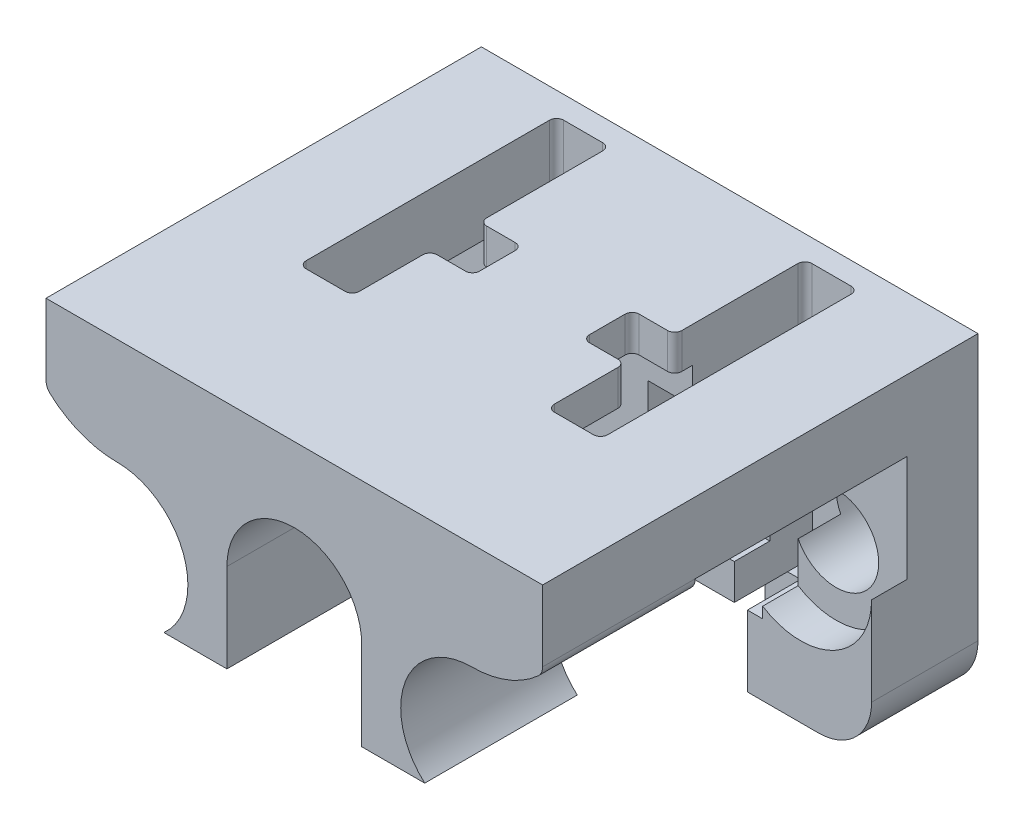
SolidWorks part; units mm, degrees
ref_plane "Front Plane" through (0, 0, 0) normal (0, 0, 1) x (1, 0, 0)
ref_plane "Top Plane" through (0, 0, 0) normal (0, 1, 0) x (1, 0, 0)
ref_plane "Right Plane" through (0, 0, 0) normal (1, 0, 0) x (0, 0, -1)
sketch "Sketch1" plane through (0, 0, 0) normal (0, 0, 1) x (1, 0, 0)
  line L1 (-7, -3.5) -> (7, -3.5)
  line L2 (-7, -3.5) -> (-7, 3.5)
  line L3 (-7, 3.5) -> (7, 3.5)
  line L4 (7, -3.5) -> (7, 3.5)
  line L5 (-7, -3.5) -> (7, 3.5) construction
  line L6 (-7, 3.5) -> (7, -3.5) construction
  point P0 (0, 0)
  dimension "D1" = 14
  dimension "D2" = 7
extrude "Boss-Extrude1" add sketch "Sketch1" along normal blind 2
fillet "Fillet1" radius 1.5 2 edges at (-7, -3.5, 1) (7, -3.5, 1)
hole_wizard "M2 Clearance Hole1" positions "Sketch2" profile "Sketch3" hole size "M2" standard "ISO" end condition through all
sketch "Sketch2" plane through (0, 0, 2) normal (0, 0, 1) x (1, 0, 0)
  line L0 (7, 3.5) -> (-7, 3.5) construction
  line L1 (0, 0) -> (0, 2.7622) construction
  point P0 (-5, 0.5)
  point P2 (5, 0.5)
  dimension "D1" = 3
  dimension "D2" = 10
sketch "Sketch3" plane through (-5, 0.5, 2) normal (1, 0, 0) x (0, -1, 0)
  line L0 (0, 0) -> (0, 2)
  line L1 (0, 2) -> (1.2, 2)
  line L2 (1.2, 2) -> (1.2, 0)
  line L5 (1.2, 0) -> (0, 0)
  line L11 (0, -6.35) -> (0, 107.95) construction
  dimension "Thru Hole Dia." = 2.4
  dimension "Thru Hole Depth" = 2
sketch "Sketch4" plane through (0, 3.5, 0) normal (0, 1, 0) x (1, 0, 0)
  line L0 (7, 0) -> (-7, 0) construction
  line L1 (-7, 0) -> (7, 0)
  line L2 (-7, 0) -> (-7, -12.2738)
  line L3 (-7, -12.2738) -> (7, -12.2738)
  line L4 (7, 0) -> (7, -12.2738)
extrude "Boss-Extrude2" add sketch "Sketch4" along normal blind 2
sketch "Sketch5" plane through (0, 0, 2) normal (0, 0, 1) x (1, 0, 0)
  line L0 (-5.5, -3.5) -> (5.5, -3.5) construction
  line L1 (-5.5, -3.5) -> (5.5, -3.5)
  line L2 (7, -2) -> (7, 3.5) construction
  line L3 (-7, 3.5) -> (-7, -2) construction
  line L4 (7, -2) -> (7, 3.5)
  line L5 (-7, 3.5) -> (-7, -2)
  line L6 (-3.2679, -0.5) -> (3.2679, -0.5)
  arc A0 (5.5, -3.5) -> (7, -2) centre (5.5, -2) ccw construction
  arc A1 (-7, -2) -> (-5.5, -3.5) centre (-5.5, -2) ccw construction
  arc A2 (5.5, -3.5) -> (7, -2) centre (5.5, -2) ccw
  arc A3 (-7, -2) -> (-5.5, -3.5) centre (-5.5, -2) ccw
  circle A4 centre (-5, 0.5) radius 2
  circle A5 centre (5, 0.5) radius 2
  arc M7 (-7, -2) -> (-5.5, -3.5) centre (-5.5, -2) ccw
  line M8 (-5.5, -3.5) -> (5.5, -3.5)
  arc M9 (5.5, -3.5) -> (7, -2) centre (5.5, -2) ccw
  line M10 (7, -2) -> (7, 3.5)
  dimension "D1" = 3
extrude "Boss-Extrude3" add sketch "Sketch5" along normal blind 1 contours A5 L6 A4 L5 M7 M8 M9 M10 region at (0, -2.1082, 2)
sketch "Sketch6" plane through (0, 0, 0) normal (0, 0, -1) x (-1, 0, 0)
  line L0 (5.5, -3.5) -> (-5.5, -3.5) construction
  line L1 (-2.5, -3.5) -> (2.5, -3.5)
  line L2 (-2.5, -3.5) -> (-2.5, 0)
  line L3 (-2.5, 0) -> (2.5, 0)
  line L4 (2.5, -3.5) -> (2.5, 0)
  line L5 (5.5, -3.5) -> (-5.5, -3.5) construction
  point P11 (0, -3.5)
  dimension "D1" = 5
  dimension "D2" = 3.5
extrude "Cut-Extrude1" cut sketch "Sketch6" against normal blind 1.5
sketch "Sketch7" plane through (0, 0, 1.5) normal (0, 0, -1) x (-1, 0, 0)
  line L1 (-3.5, -3.5) -> (3.5, -3.5)
  line L2 (-3.5, -3.5) -> (-3.5, -1.5)
  line L3 (-3.5, -1.5) -> (3.5, -1.5)
  line L4 (3.5, -3.5) -> (3.5, -1.5)
  line L5 (-2.5, -3.5) -> (-5.5, -3.5) construction
  point P5 (0, -3.5)
  dimension "D1" = 2
  dimension "D2" = 7
extrude "Cut-Extrude2" cut sketch "Sketch7" against normal up to next
sketch "Sketch8" plane through (0, 0, 2) normal (0, 0, 1) x (1, 0, 0)
  line L1 (-1.5, -1.5) -> (1.5, -1.5)
  line L2 (-1.5, -1.5) -> (-1.5, 3.5)
  line L3 (-1.5, 3.5) -> (1.5, 3.5)
  line L4 (1.5, -1.5) -> (1.5, 3.5)
  line L5 (7, 3.5) -> (-7, 3.5) construction
  line L6 (-3.5, -1.5) -> (3.5, -1.5) construction
  circle A0 centre (-5, 0.5) radius 2
  circle A1 centre (5, 0.5) radius 2
  arc A2 (3.2679, -0.5) -> (7, 0.5) centre (5, 0.5) ccw construction
  point P17 (0, -1.5)
  line M8 (-3.2679, -0.5) -> (3.2679, -0.5)
  line M12 (7, 3.5) -> (-7, 3.5)
  dimension "D1" = 3
extrude "Boss-Extrude4" add sketch "Sketch8" along normal blind 1.8 contours L4 L2 M8 M12 | L1 L4 L2 M8 region at (0, -1, 2) region at (0, 1.5, 2)
sketch "Sketch9" plane through (0, 5.5, 0) normal (0, 1, 0) x (1, 0, 0)
  line L0 (7, 0) -> (-7, 0) construction
  line L1 (-2.95, -7.89) -> (-4.05, -7.89)
  line L2 (-2.75, -7.69) -> (-2.75, -5.9)
  line L3 (-2.95, -0.63) -> (-4.05, -0.63)
  line L4 (-4.25, -7.69) -> (-4.25, -0.83)
  line L5 (-7, 0) -> (-7, -12.2738) construction
  line L6 (0, 0) -> (0, -11.1853) construction
  line L11 (-2.55, -5.7) -> (-1.75, -5.7)
  line L12 (-1.55, -5.5) -> (-1.55, -4.5)
  line L13 (-1.75, -4.3) -> (-2.55, -4.3)
  line L14 (-2.75, -4.1) -> (-2.75, -0.83)
  line L15 (2.75, -4.1) -> (2.75, -0.83)
  line L16 (1.75, -4.3) -> (2.55, -4.3)
  line L17 (1.55, -5.5) -> (1.55, -4.5)
  line L18 (2.55, -5.7) -> (1.75, -5.7)
  line L19 (4.25, -7.69) -> (4.25, -0.83)
  line L20 (2.95, -0.63) -> (4.05, -0.63)
  line L21 (2.75, -7.69) -> (2.75, -5.9)
  line L22 (2.95, -7.89) -> (4.05, -7.89)
  arc A0 (-2.95, -7.89) -> (-2.75, -7.69) centre (-2.95, -7.69) ccw
  arc A1 (-2.75, -0.83) -> (-2.95, -0.63) centre (-2.95, -0.83) ccw
  arc A2 (-4.05, -0.63) -> (-4.25, -0.83) centre (-4.05, -0.83) ccw
  arc A3 (-4.05, -7.89) -> (-4.25, -7.69) centre (-4.05, -7.69) cw
  arc A8 (-2.55, -5.7) -> (-2.75, -5.9) centre (-2.55, -5.9) ccw
  arc A9 (-1.75, -5.7) -> (-1.55, -5.5) centre (-1.75, -5.5) ccw
  arc A10 (-1.55, -4.5) -> (-1.75, -4.3) centre (-1.75, -4.5) ccw
  arc A11 (-2.55, -4.3) -> (-2.75, -4.1) centre (-2.55, -4.1) cw
  arc A12 (2.55, -4.3) -> (2.75, -4.1) centre (2.55, -4.1) ccw
  arc A13 (1.55, -4.5) -> (1.75, -4.3) centre (1.75, -4.5) cw
  arc A14 (1.75, -5.7) -> (1.55, -5.5) centre (1.75, -5.5) cw
  arc A15 (2.55, -5.7) -> (2.75, -5.9) centre (2.55, -5.9) cw
  arc A16 (4.05, -7.89) -> (4.25, -7.69) centre (4.05, -7.69) ccw
  arc A17 (4.05, -0.63) -> (4.25, -0.83) centre (4.05, -0.83) cw
  arc A18 (2.75, -0.83) -> (2.95, -0.63) centre (2.95, -0.83) cw
  arc A19 (2.95, -7.89) -> (2.75, -7.69) centre (2.95, -7.69) cw
  point P12 (-2.75, -7.89)
  point P15 (-2.75, -0.63)
  point P18 (-4.25, -0.63)
  point P51 (-2.75, -4.3)
  point P61 (2.75, -4.3)
  point P62 (4.25, -0.63)
  point P63 (2.75, -0.63)
  point P64 (2.75, -7.89)
  dimension "D5" = 0.2
  dimension "D9" = 0.2
  dimension "D1" = 1.5
  dimension "D2" = 7.26
  dimension "D3" = 0.63
  dimension "D4" = 2.75
  dimension "D6" = 1.2
  dimension "D7" = 1.4
  dimension "D8" = 4.3
extrude "Cut-Extrude3" cut sketch "Sketch9" against normal up to surface (2 mm away) up to face at (0, 3.5, 5.0184)
sketch "Sketch10" plane through (0, 3.5, 0) normal (0, -1, 0) x (1, 0, 0)
  line L1 (4.05, 7.89) -> (-4.05, 7.89)
  line L2 (4.05, 7.89) -> (4.05, 3.8)
  line L3 (4.05, 3.8) -> (-4.05, 3.8)
  line L4 (-4.05, 7.89) -> (-4.05, 3.8)
  line L5 (1.5, 3.8) -> (-1.5, 3.8) construction
extrude "Cut-Extrude4" cut sketch "Sketch10" against normal blind 1
sketch "Sketch12" plane through (0, 0, 12.2738) normal (0, 0, 1) x (1, 0, 0)
  line L0 (-7, 3.5) -> (-7, -1)
  line L1 (-7, 0.5) -> (-7, -2) construction
  line L2 (-7, -1) -> (-1.9, -1)
  line L3 (-1.9, -1) -> (-1.9, 1.5)
  line L4 (1.9, 1.5) -> (1.9, -1)
  line L5 (1.9, -1) -> (7, -1)
  line L6 (7, -2) -> (7, 0.5) construction
  line L7 (7, -1) -> (7, 3.5)
  line L8 (7, 3.5) -> (-7, 3.5)
  line L9 (0, 0) -> (0, 6.7843) construction
  line L12 (7, 5.5) -> (7, 3.5) construction
  arc A0 (-1.9, 1.5) -> (1.9, 1.5) centre (0, 1.5) cw
  circle A1 centre (5, 0.5) radius 2
  arc A2 (6.8737, 3.2171) -> (7, 3.5) centre (6.62, 3.5) ccw
  arc A3 (6.8737, 3.2171) -> (5, 2.5) centre (5, 5.3065) cw
  circle A4 centre (-5, 0.5) radius 2
  arc A5 (-6.8737, 3.2171) -> (-5, 2.5) centre (-5, 5.3065) ccw
  arc A6 (-6.8737, 3.2171) -> (-7, 3.5) centre (-6.62, 3.5) cw
  line M9 (-7, 3.5) -> (7, 3.5)
  dimension "D1" = 1.9
  dimension "D4" = 4
  dimension "D5" = 0.38
  dimension "D2" = 2
  dimension "D3" = 4.5
extrude "Boss-Extrude5" add sketch "Sketch12" against normal blind 4.3 contours L8 A0 L4 L5 L7 | L3 A0 L0 L2 M9 region at (0, 3.4853, 12.2738)
sketch "Sketch13" plane through (0, 3.5, 0) normal (0, 1, 0) x (1, 0, 0)
  line L0 (3.2679, -3) -> (7, -3) construction
  line L1 (3.93, -3) -> (3.13, -3)
  line L2 (3.93, -3) -> (3.93, -0.8)
  line L3 (3.93, -0.8) -> (3.13, -0.8)
  line L4 (3.13, -3) -> (3.13, -0.8)
  line L6 (4.25, -7.69) -> (4.25, -0.83) construction
  point P7 (3.53, -0.8)
  dimension "D1" = 0.8
  dimension "D2" = 2.2
  dimension "D3" = 0.72
extrude "Cut-Extrude5" cut sketch "Sketch13" against normal blind 5
mirror "Mirror1" about plane through (0, 0, 0) normal (1, 0, 0) of "Cut-Extrude5"
